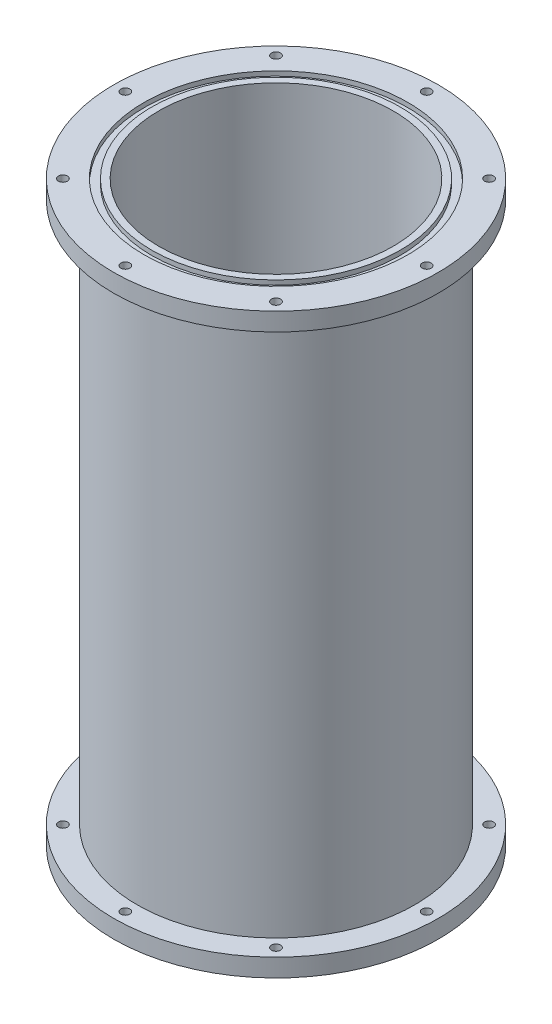
SolidWorks part; units mm, degrees
material "6061-T6 (SS)"
ref_plane "Front Plane" through (0, 0, 0) normal (0, 0, 1) x (1, 0, 0)
ref_plane "Top Plane" through (0, 0, 0) normal (0, 1, 0) x (1, 0, 0)
ref_plane "Right Plane" through (0, 0, 0) normal (1, 0, 0) x (0, 0, -1)
sketch "Sketch3" plane through (0, 0, 0) normal (0, 1, 0) x (1, 0, 0)
  circle A0 centre (0, 0) radius 32.5
  circle A1 centre (0, 0) radius 38.5
extrude "Boss-Extrude3" add sketch "Sketch3" along normal blind 160
sketch "Sketch5" plane through (0, 0, 0) normal (0, -1, 0) x (1, 0, 0)
  circle A0 centre (0, 0) radius 45
  circle A1 centre (0, 0) radius 32.5
  circle A2 centre (0, 0) radius 35.6743
  circle A3 centre (0, 0) radius 36.7411
  circle A4 centre (0, 0) radius 34.6075
  circle M1 centre (0, 0) radius 38.5
extrude "Cut-Extrude1" cut sketch "Sketch5" against normal blind 1.4224 contours A3 A2 | A2 A4 region at (-34.6653, 0, 0) region at (-35.7019, 0, 0)
extrude "Boss-Extrude5" add sketch "Sketch5<4>" against normal blind 5 contours A0 M1 region at (-43.7272, 0, 0)
sketch "Sketch5<4>" plane through (0, 0, 0) normal (0, -1, 0) x (1, 0, 0) same geometry as "Sketch5"
sketch "Sketch7" plane through (0, 5, 0) normal (0, 1, 0) x (1, 0, 0)
  circle A3 centre (0, 41.75) radius 1.55
  circle A4 centre (29.5217, 29.5217) radius 1.55
  circle A5 centre (41.75, 0) radius 1.55
  circle A6 centre (29.5217, -29.5217) radius 1.55
  circle A7 centre (0, -41.75) radius 1.55
  circle A8 centre (-29.5217, -29.5217) radius 1.55
  circle A9 centre (-41.75, 0) radius 1.55
  circle A10 centre (-29.5217, 29.5217) radius 1.55
  point P20 (0, 0)
  dimension "D1" = 8
extrude "Cut-Extrude2" cut sketch "Sketch7" against normal blind 5
sketch "Sketch9" plane through (0, 160, 0) normal (0, 1, 0) x (1, 0, 0)
  circle A0 centre (0, 0) radius 32.5
  circle A1 centre (0, 0) radius 38.5
extrude "Cut-Extrude3" cut sketch "Sketch9" against normal blind 80
mirror "Mirror7" about plane through (0, 80, 0) normal (0, 1, 0) of "Boss-Extrude3", "Cut-Extrude1", "Boss-Extrude5", "Cut-Extrude2"
extrude "Cut-Extrude6" cut sketch "Sketch5<7>" against normal blind 1.4224 contours A3 A2 | A2 A4 region at (-34.6653, 0, 0) region at (-35.7019, 0, 0)
sketch "Sketch5<7>" plane through (0, 0, 0) normal (0, -1, 0) x (1, 0, 0) same geometry as "Sketch5"
sketch "Sketch10" plane through (0, 160, 0) normal (0, 1, 0) x (1, 0, 0)
  circle A0 centre (0, 0) radius 34.6075
  circle A1 centre (0, 0) radius 36.7411
extrude "Boss-Extrude6" add sketch "Sketch10" against normal up to surface (160 mm away) up to face at (0, 0, -36.7411)
sketch "Sketch11" plane through (0, 160, 0) normal (0, 1, 0) x (1, 0, 0)
  circle A0 centre (0, 0) radius 36.5633
  circle A1 centre (0, 0) radius 34.4043
extrude "Cut-Extrude7" cut sketch "Sketch11" against normal blind 1.27
sketch "Sketch12" plane through (0, 0, 0) normal (0, -1, 0) x (1, 0, 0)
  circle A0 centre (0, 0) radius 36.5633
  circle A1 centre (0, 0) radius 34.4043
extrude "Cut-Extrude8" cut sketch "Sketch12" against normal blind 1.27
sketch "Sketch15" plane through (0, 160, 0) normal (0, 1, 0) x (1, 0, 0)
  circle A0 centre (0, 0) radius 36.5633
  circle A1 centre (0, 0) radius 45
extrude "Boss-Extrude7" add sketch "Sketch15" against normal up to surface (5 mm away) up to face at (-29.5217, 155, -27.9717)
sketch "Sketch16" plane through (0, 0, 0) normal (0, -1, 0) x (1, 0, 0)
  circle A0 centre (0, 0) radius 36.5633
  circle A1 centre (0, 0) radius 45
extrude "Boss-Extrude8" add sketch "Sketch16" against normal up to surface (5 mm away) up to face at (-29.5217, 5, -27.9717)
sketch "Sketch19" plane through (0, 160, 0) normal (0, 1, 0) x (1, 0, 0)
  point P0 (29.5217, 29.5217)
  point P3 (41.75, 0)
  point P5 (29.5217, -29.5217)
  point P6 (0, -41.75)
  point P7 (0, 41.75)
  point P8 (-29.5217, -29.5217)
  point P9 (-41.75, 0)
  point P10 (-29.5217, 29.5217)
  point P11 (0, 0)
  dimension "D1" = 8
hole_wizard "M3 Tapped Hole1" positions "Sketch19" profile "Sketch20" tap size "M3" standard "DIN"
sketch "Sketch20" plane through (29.5217, 160, -29.5217) normal (1, 0, 0) x (0, 0, 1)
  line L0 (0, 0) -> (0, 5.7511)
  line L1 (0, 5.7511) -> (1.25, 5)
  line L2 (1.25, 5) -> (1.25, 0)
  line L5 (1.25, 0) -> (0, 0)
  line L10 (0, 5.7511) -> (-1.25, 5) construction
  line L11 (0, -6.35) -> (0, 107.95) construction
  dimension "Tap Drill Dia." = 2.5
  dimension "Tap Drill Depth" = 5
  dimension "Drill Angle" = 118
cosmetic thread "Hole Thread1" parameters "D1"=10, "D2"=3
cosmetic thread "Hole Thread2" parameters "D1"=10, "D2"=3
cosmetic thread "Hole Thread3" parameters "D1"=10, "D2"=3
cosmetic thread "Hole Thread4" parameters "D1"=10, "D2"=3
cosmetic thread "Hole Thread5" parameters "D1"=10, "D2"=3
cosmetic thread "Hole Thread6" parameters "D1"=10, "D2"=3
cosmetic thread "Hole Thread7" parameters "D1"=10, "D2"=3
cosmetic thread "Hole Thread8" parameters "D1"=10, "D2"=3
sketch "Sketch21" plane through (0, 0, 0) normal (0, -1, 0) x (1, 0, 0)
  point P0 (29.5217, 29.5217)
  point P4 (41.75, 0)
  point P5 (29.5217, -29.5217)
  point P6 (0, -41.75)
  point P8 (0, 41.75)
  point P9 (-29.5217, -29.5217)
  point P10 (-41.75, 0)
  point P11 (-29.5217, 29.5217)
  point P12 (0, 0)
  dimension "D1" = 8
hole_wizard "M3 Tapped Hole2" positions "Sketch21" profile "Sketch22" tap size "M3" standard "DIN"
sketch "Sketch22" plane through (29.5217, 0, 29.5217) normal (1, 0, 0) x (0, 0, -1)
  line L0 (0, 0) -> (0, 5.7511)
  line L1 (0, 5.7511) -> (1.25, 5)
  line L2 (1.25, 5) -> (1.25, 0)
  line L5 (1.25, 0) -> (0, 0)
  line L10 (0, 5.7511) -> (-1.25, 5) construction
  line L11 (0, -6.35) -> (0, 107.95) construction
  dimension "Tap Drill Dia." = 2.5
  dimension "Tap Drill Depth" = 5
  dimension "Drill Angle" = 118
cosmetic thread "Hole Thread9" parameters "D1"=10, "D2"=3
cosmetic thread "Hole Thread10" parameters "D1"=10, "D2"=3
cosmetic thread "Hole Thread11" parameters "D1"=10, "D2"=3
cosmetic thread "Hole Thread12" parameters "D1"=10, "D2"=3
cosmetic thread "Hole Thread13" parameters "D1"=10, "D2"=3
cosmetic thread "Hole Thread14" parameters "D1"=10, "D2"=3
cosmetic thread "Hole Thread15" parameters "D1"=10, "D2"=3
cosmetic thread "Hole Thread16" parameters "D1"=10, "D2"=3
